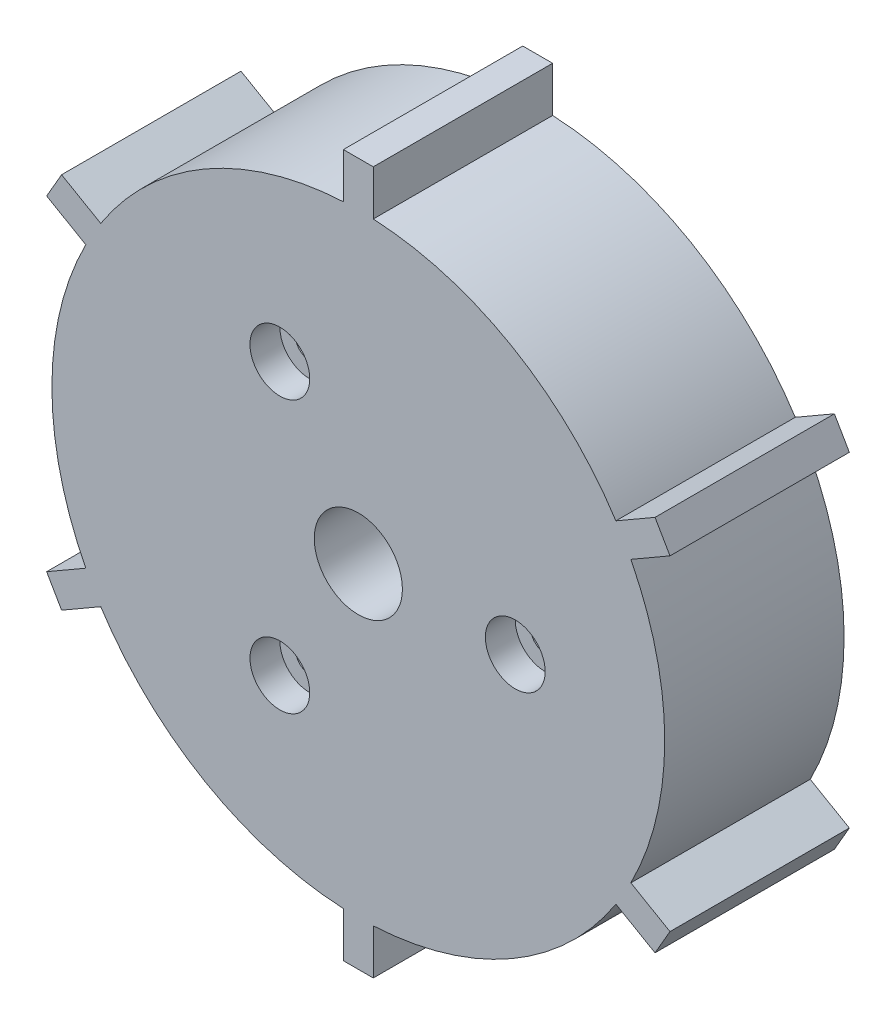
SolidWorks part; units mm, degrees
other "Markup1"
sketch "Sketch3" plane through (-20.8516, -23.5, 5) normal (0, 0, 1) x (1, 0, 0)
ref_plane "Front Plane" through (0, 0, 0) normal (0, 0, 1) x (1, 0, 0)
ref_plane "Top Plane" through (0, 0, 0) normal (0, 1, 0) x (1, 0, 0)
ref_plane "Right Plane" through (0, 0, 0) normal (1, 0, 0) x (0, 0, -1)
sketch "Sketch1" plane through (0, 0, 0) normal (0, 0, 1) x (1, 0, 0)
  line L5 (19.8516, 12.616) -> (17.2324, 11.1038)
  line L6 (-1, 23.5) -> (1, 23.5)
  line L30 (-1, 23.5) -> (-1, 20.4756)
  line L31 (-1, -23.5) -> (1, -23.5)
  line L32 (1, 23.5) -> (1, 20.4756)
  line L33 (-1, 23.5) -> (1, -23.5) construction
  line L34 (-1, -23.5) -> (1, 23.5) construction
  line L35 (19.8516, 12.616) -> (20.8516, 10.884)
  line L36 (20.8516, 10.884) -> (18.2324, 9.3718)
  line L37 (-20.8516, -10.884) -> (-19.8516, -12.616)
  line L38 (20.8516, -10.884) -> (18.2324, -9.3718)
  line L39 (20.8516, -10.884) -> (19.8516, -12.616)
  line L40 (19.8516, -12.616) -> (17.2324, -11.1038)
  line L41 (-19.8516, 12.616) -> (-20.8516, 10.884)
  line L42 (1, -23.5) -> (1, -20.4756)
  line L43 (1, -23.5) -> (-1, -23.5)
  line L44 (-1, -23.5) -> (-1, -20.4756)
  line L45 (1, 23.5) -> (-1, 23.5)
  line L46 (-19.8516, -12.616) -> (-17.2324, -11.1038)
  line L47 (-19.8516, -12.616) -> (-20.8516, -10.884)
  line L48 (-20.8516, -10.884) -> (-18.2324, -9.3718)
  line L49 (20.8516, 10.884) -> (19.8516, 12.616)
  line L50 (-20.8516, 10.884) -> (-18.2324, 9.3718)
  line L51 (-20.8516, 10.884) -> (-19.8516, 12.616)
  line L52 (-19.8516, 12.616) -> (-17.2324, 11.1038)
  line L65 (19.8516, -12.616) -> (20.8516, -10.884)
  line L66 (-17.2324, 11.1038) -> (-19.8516, 12.616)
  line L67 (18.2324, -9.3718) -> (20.8516, -10.884)
  line L68 (-18.2324, 9.3718) -> (-20.8516, 10.884)
  line L69 (17.2324, -11.1038) -> (19.8516, -12.616)
  line L70 (-18.2324, -9.3718) -> (-20.8516, -10.884)
  line L71 (17.2324, 11.1038) -> (19.8516, 12.616)
  line L72 (-17.2324, -11.1038) -> (-19.8516, -12.616)
  line L73 (18.2324, 9.3718) -> (20.8516, 10.884)
  line L74 (1, -20.4756) -> (1, -23.5)
  line L75 (1, 20.4756) -> (1, 23.5)
  line L76 (-1, -20.4756) -> (-1, -23.5)
  line L77 (-1, 20.4756) -> (-1, 23.5)
  circle A0 centre (0, 0) radius 18.5
  arc A1 (-18.2324, 9.3718) -> (-18.2324, -9.3718) centre (0, 0) ccw
  circle A2 centre (0, 0) radius 2.9491
  arc A4 (-0.8716, 20.4815) -> (-17.2324, 11.1038) centre (0, 0) ccw
  arc A5 (17.2324, 11.1038) -> (0.8716, 20.4815) centre (0, 0) ccw
  arc A6 (-17.2324, -11.1038) -> (-0.8716, -20.4815) centre (0, 0) ccw
  arc A7 (0.8716, -20.4815) -> (17.2324, -11.1038) centre (0, 0) ccw
  circle A8 centre (-5.25, 9.09) radius 0.95
  circle A9 centre (10.5, 0) radius 0.95
  circle A10 centre (-5.25, -9.09) radius 0.95
  arc A11 (18.2324, -9.3718) -> (18.2324, 9.3718) centre (0, 0) ccw
  point P32 (0, 0)
  point P35 (0, 0)
  dimension "D2" = 2
  dimension "D6" = 1.9
  dimension "D7" = 1.9
  dimension "D8" = 1.9
  dimension "D9" = 5.25
  dimension "D10" = 9.09
  dimension "D11" = 9.09
  dimension "D12" = 5.25
  dimension "D4" = 23.5
  dimension "D3" = 2
  dimension "D13" = 10.5
  dimension "D5" = 6
extrude "Boss-Extrude1" add sketch "Sketch1" along normal blind 5 contours A0 A10 A9 A8 A2 | L41 L37 L6 L40 L39 L35 A0 region at (19.8074, 11.4358, 0) region at (-17.9767, 0, 0)
sketch "Sketch2" plane through (0, 0, 5) normal (0, 0, 1) x (1, 0, 0)
  circle A0 centre (-5.25, 9.09) radius 2
  circle A1 centre (-5.25, -9.09) radius 2
  circle A2 centre (10.5, 0) radius 2
  dimension "D1" = 4
  dimension "D2" = 4
  dimension "D3" = 4
extrude "Cut-Extrude1" cut sketch "Sketch2" against normal blind 2
extrude "Boss-Extrude2" add sketch "Sketch1<3>" against normal blind 7 contours L41 L37 L6 L40 L39 L35 A0 region at (19.8074, 11.4358, 0)
sketch "Sketch1<3>" plane through (0, 0, 0) normal (0, 0, 1) x (1, 0, 0) same geometry as "Sketch1"
